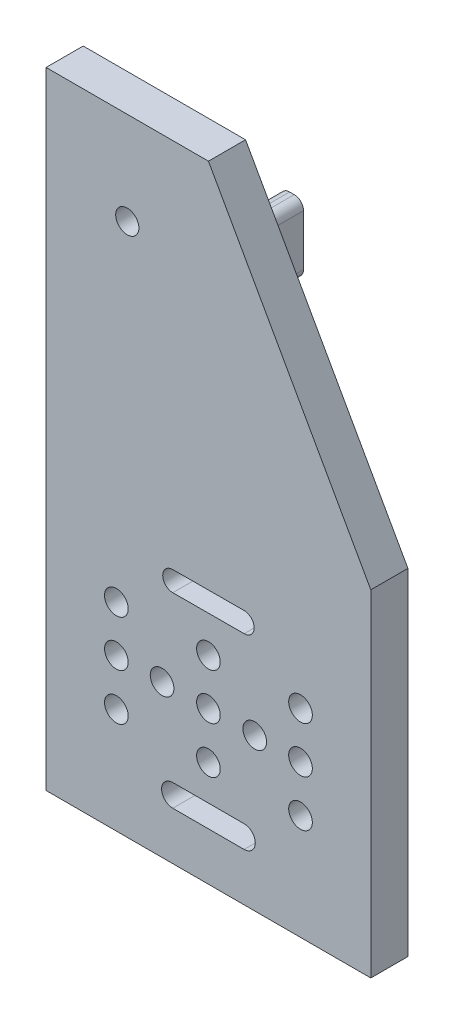
SolidWorks part; units mm, degrees
ref_plane "Plan de face" through (0, 0, 0) normal (0, 0, 1) x (1, 0, 0)
ref_plane "Plan de dessus" through (0, 0, 0) normal (0, 1, 0) x (1, 0, 0)
ref_plane "Plan de droite" through (0, 0, 0) normal (1, 0, 0) x (0, 0, -1)
sketch "Esquisse1" plane through (0, 0, 0) normal (0, 0, 1) x (1, 0, 0)
  line L0 (0, 135) -> (35, 135) construction
  line L1 (0, 0) -> (70, 0)
  line L2 (0, 0) -> (0, 135)
  line L3 (0, 135) -> (35, 135)
  line L4 (70, 0) -> (70, 72.4723)
  line L5 (35, 135) -> (70, 72.4723) construction
  line L6 (35, 135) -> (70, 72.4723)
  line L7 (17.5, 135) -> (17.5, 115) construction
  circle A0 centre (17.5, 115) radius 2.5
  dimension "D1" = 70
  dimension "D2" = 135
  dimension "D3" = 20
extrude "Boss.-Extru.1" add sketch "Esquisse1" along normal blind 8
sketch "Esquisse3" plane through (0, 0, 0) normal (0, 0, -1) x (-1, 0, 0)
  line L0 (-35, 0) -> (-35, 38.3731) construction
  line L1 (0, 0) -> (-70, 0) construction
ref_axis "Axe1" through (35, -13.1714, 0) along (0, 1, 0)
sketch "Esquisse4" plane through (0, 0, 0) normal (0, 0, -1) x (-1, 0, 0)
  line L0 (-17.5, 115) -> (-17.5, 105) construction
  line L1 (-27.4969, 105) -> (-7.5031, 105)
  line L2 (-7.5031, 105) -> (-7.5031, 113)
  line L3 (-5.5031, 115) -> (-4.5044, 115)
  line L4 (-2.5044, 113) -> (-2.5044, 102.0044)
  line L5 (-4.5044, 100.0044) -> (-30.4956, 100.0044)
  line L6 (-32.4956, 113) -> (-32.4956, 102.0044)
  line L7 (-29.4969, 115) -> (-30.4956, 115)
  line L8 (-27.4969, 105) -> (-27.4969, 113)
  arc A0 (-29.4969, 115) -> (-27.4969, 113) centre (-29.4969, 113) cw
  arc A1 (-32.4956, 113) -> (-30.4956, 115) centre (-30.4956, 113) cw
  arc A2 (-32.4956, 102.0044) -> (-30.4956, 100.0044) centre (-30.4956, 102.0044) ccw
  arc A3 (-2.5044, 102.0044) -> (-4.5044, 100.0044) centre (-4.5044, 102.0044) cw
  arc A4 (-7.5031, 113) -> (-5.5031, 115) centre (-5.5031, 113) cw
  arc A5 (-4.5044, 115) -> (-2.5044, 113) centre (-4.5044, 113) cw
  point P9 (-17.5, 100.0044)
  point P14 (-27.4969, 115)
  point P17 (-32.4956, 115)
  point P20 (-32.4956, 100.0044)
  point P23 (-2.5044, 100.0044)
  point P26 (-7.5031, 115)
  point P29 (-2.5044, 115)
  dimension "D2" = 2
  dimension "D1" = 10
extrude "Boss.-Extru.3" add sketch "Esquisse4" along normal blind 15
fillet "Congé1" radius 1 13 edges at (27.4969, 109, 0) (28.0826, 114.4142, 0) (29.9962, 115, 0) (31.9098, 114.4142, 0) (32.4956, 107.5022, 0) (31.9098, 100.5902, 0) (17.5, 100.0044, 0) (7.5031, 109, 0) (6.9174, 114.4142, 0) (5.0038, 115, 0) (3.0902, 114.4142, 0) (2.5044, 107.5022, 0) (3.0902, 100.5902, 0)
sketch "Esquisse5" plane through (0, 0, 0) normal (0, 0, -1) x (-1, 0, 0)
  circle A0 centre (-54.85, 52.7483) radius 3.75
  circle A1 centre (-15.15, 52.7483) radius 3.75
  circle A2 centre (-54.85, 12.75) radius 3.75
  circle A3 centre (-15.15, 12.75) radius 3.75
extrude "Enlèv. mat.-Extru.1" cut sketch "Esquisse5" against normal blind 1.75
sketch "Esquisse6" plane through (0, 0, 0) normal (0, 0, -1) x (-1, 0, 0)
  circle A0 centre (-54.8469, 42.7525) radius 2.55
  circle A1 centre (-34.9977, 42.7525) radius 2.55
  circle A2 centre (-54.8469, 32.7887) radius 2.55
  circle A3 centre (-44.9846, 32.7887) radius 2.55
  circle A4 centre (-34.9977, 32.7887) radius 2.55
  circle A5 centre (-25.0004, 32.7887) radius 2.55
  circle A6 centre (-15.1504, 42.7525) radius 2.55
  circle A7 centre (-15.15, 32.7887) radius 2.55
  circle A8 centre (-15.15, 22.7468) radius 2.55
  circle A9 centre (-34.9977, 22.7468) radius 2.55
  circle A10 centre (-54.8469, 22.7468) radius 2.55
extrude "Enlèv. mat.-Extru.2" cut sketch "Esquisse6" against normal through all
sketch "Esquisse7" plane through (0, 0, 0) normal (0, 0, -1) x (-1, 0, 0)
  line L0 (-35, 55.0483) -> (-35, 50.4483) construction
  line L1 (-42.6949, 55.0483) -> (-27.3051, 55.0483) construction
  line L2 (-27.3051, 50.4483) -> (-42.6949, 50.4483) construction
  line L3 (-35, 52.7705) -> (-27.3051, 52.7483) construction
  line L4 (-42.6949, 52.7927) -> (-27.3051, 52.7483) construction
  line L5 (-42.6887, 54.9535) -> (-27.2988, 54.909)
  line L6 (-42.7012, 50.632) -> (-27.3113, 50.5876)
  line L7 (-35, 15.25) -> (-35, 10.25) construction
  line L8 (-42.6949, 15.25) -> (-27.3051, 15.25) construction
  line L9 (-27.3051, 10.25) -> (-42.6949, 10.25) construction
  line L10 (-35, 10.25) -> (-35, 12.75) construction
  line L11 (-35, 12.75) -> (-27.3051, 12.75) construction
  line L12 (-42.6949, 12.75) -> (-27.3051, 12.75) construction
  line L13 (-42.6949, 15.1528) -> (-27.3051, 15.1528)
  line L14 (-42.6949, 10.3472) -> (-27.3051, 10.3472)
  arc A0 (-42.6887, 54.9535) -> (-42.7012, 50.632) centre (-42.6949, 52.7927) ccw
  arc A1 (-27.3113, 50.5876) -> (-27.2988, 54.909) centre (-27.3051, 52.7483) ccw
  arc A2 (-42.6949, 15.1528) -> (-42.6949, 10.3472) centre (-42.6949, 12.75) ccw
  arc A3 (-27.3051, 10.3472) -> (-27.3051, 15.1528) centre (-27.3051, 12.75) ccw
  point P10 (-35, 52.7705)
  point P25 (-35, 12.75)
extrude "Enlèv. mat.-Extru.3" cut sketch "Esquisse7" against normal through all
sketch "Esquisse8" plane through (0, 0, 0) normal (0, 0, -1) x (-1, 0, 0)
  line L0 (-54.85, 61.9498) -> (-54.85, 58.9498) construction
  line L1 (-58.0962, 61.9498) -> (-51.6038, 61.9498) construction
  line L2 (-51.6038, 58.9498) -> (-58.0962, 58.9498) construction
  line L3 (-58.0962, 60.4498) -> (-51.6038, 60.4498) construction
  line L4 (-58.0962, 61.8873) -> (-51.6038, 61.8873)
  line L5 (-58.0962, 59.0123) -> (-51.6038, 59.0123)
  line L6 (-35, 65.5) -> (-35, 53.1144) construction
  line L7 (-35, 65.5) -> (-35, 0) construction
  line L8 (-11.9038, 60.4498) -> (-18.3962, 60.4498) construction
  line L9 (-11.9038, 61.8873) -> (-18.3962, 61.8873)
  line L10 (-11.9038, 59.0123) -> (-18.3962, 59.0123)
  line L11 (-54.8469, 32.7887) -> (-77.5585, 32.7887) construction
  line L12 (-58.0962, 5.1276) -> (-51.6038, 5.1276) construction
  line L13 (-58.0962, 3.6901) -> (-51.6038, 3.6901)
  line L14 (-58.0962, 6.5651) -> (-51.6038, 6.5651)
  line L15 (-11.9038, 5.1276) -> (-18.3962, 5.1276) construction
  line L16 (-11.9038, 3.6901) -> (-18.3962, 3.6901)
  line L17 (-11.9038, 6.5651) -> (-18.3962, 6.5651)
  arc A0 (-58.0962, 61.8873) -> (-58.0962, 59.0123) centre (-58.0962, 60.4498) ccw
  arc A1 (-51.6038, 59.0123) -> (-51.6038, 61.8873) centre (-51.6038, 60.4498) ccw
  arc A2 (-11.9038, 61.8873) -> (-11.9038, 59.0123) centre (-11.9038, 60.4498) cw
  arc A3 (-18.3962, 59.0123) -> (-18.3962, 61.8873) centre (-18.3962, 60.4498) cw
  arc A4 (-58.0962, 3.6901) -> (-58.0962, 6.5651) centre (-58.0962, 5.1276) cw
  arc A5 (-51.6038, 6.5651) -> (-51.6038, 3.6901) centre (-51.6038, 5.1276) cw
  arc A6 (-11.9038, 3.6901) -> (-11.9038, 6.5651) centre (-11.9038, 5.1276) ccw
  arc A7 (-18.3962, 6.5651) -> (-18.3962, 3.6901) centre (-18.3962, 5.1276) ccw
  point P8 (-54.85, 60.4498)
  point P21 (-15.15, 60.4498)
  point P31 (-54.85, 5.1276)
  point P38 (-15.15, 5.1276)
extrude "Boss.-Extru.4" add sketch "Esquisse8" along normal blind 3
fillet "Congé2" radius 0.5 16 edges at (19.8337, 5.1276, -3) (15.15, 6.5651, -3) (59.5337, 5.1276, -3) (54.85, 6.5651, -3) (19.8337, 60.4498, -3) (15.15, 61.8873, -3) (59.5337, 60.4498, -3) (54.85, 61.8873, -3) (15.15, 3.6901, -3) (10.4663, 5.1276, -3) (54.85, 3.6901, -3) (50.1663, 5.1276, -3) (15.15, 59.0123, -3) (10.4663, 60.4498, -3) (54.85, 59.0123, -3) (50.1663, 60.4498, -3)
